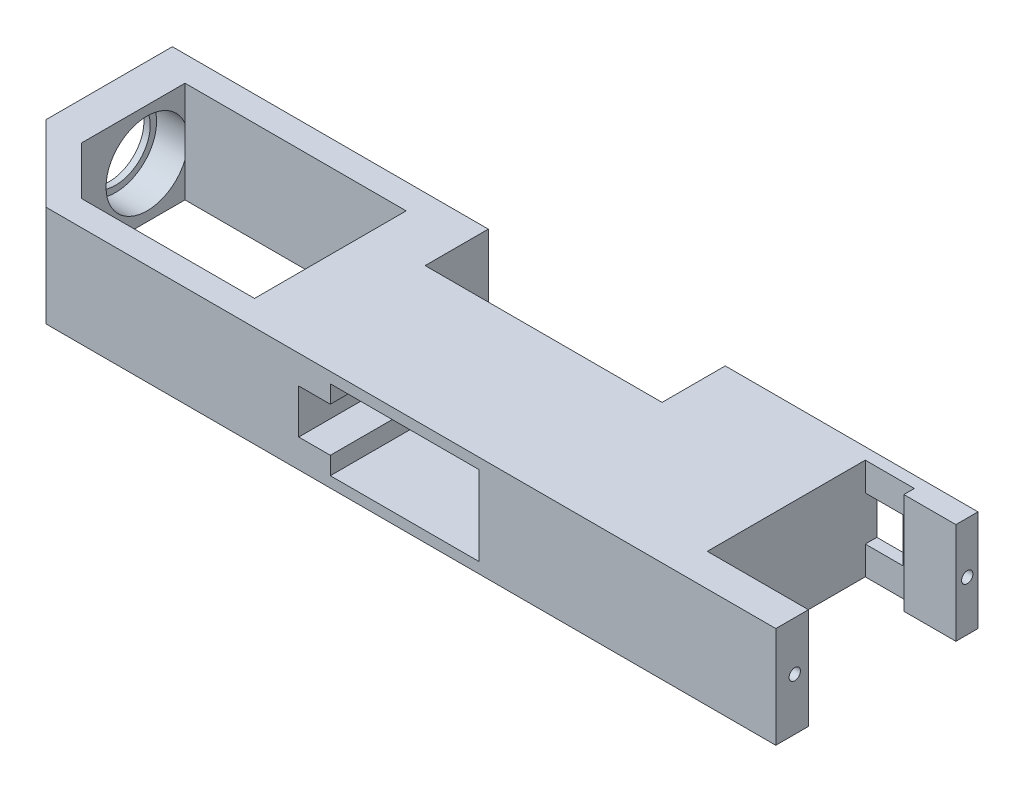
SolidWorks part; units mm, degrees
ref_plane "Front Plane" through (0, 0, 0) normal (0, 0, 1) x (1, 0, 0)
ref_plane "Top Plane" through (0, 0, 0) normal (0, 1, 0) x (1, 0, 0)
ref_plane "Right Plane" through (0, 0, 0) normal (1, 0, 0) x (0, 0, -1)
ref_axis "Axis1" through (0, 0, -88.99) along (0, 0, 1)
ref_axis "Axis2" through (88.99, 0, 0) along (-1, 0, 0)
sketch "Sketch1" plane through (0, 0, 0) normal (0, 1, 0) x (1, 0, 0)
  line L0 (64, -16.836) -> (47.9935, -16.836)
  line L1 (-63.5, 10) -> (64, 10)
  line L2 (-63.5, 10) -> (-63.5, -10)
  line L3 (-51.5, -22) -> (64, -22)
  line L4 (64, 10) -> (64, 6.5)
  line L5 (47.9935, -16.836) -> (47.9935, 8.164)
  line L6 (-63.5, -10) -> (-51.5, -22)
  line L8 (47.9935, 8.164) -> (55.7639, 8.164)
  line L9 (55.7639, 8.164) -> (55.7639, 6.5)
  line L10 (55.7639, 6.5) -> (64, 6.5)
  line L11 (64, -16.836) -> (64, -22)
  point P2 (-63.5, 0)
  dimension "D1" = 127.5
  dimension "D2" = 32
  dimension "D3" = 20
  dimension "D4" = 63.5
  dimension "D5" = 45
  dimension "D6" = 5.164
  dimension "D7" = 16.0065
  dimension "D8" = 25
  dimension "D9" = 3.5
  dimension "D10" = 8.2361
extrude "Boss-Extrude1" add sketch "Sketch1" along normal blind 8 and the other way blind 8
sketch "Sketch2" plane through (-63.5, 0, 0) normal (-1, 0, 0) x (0, 0, 1)
  circle A0 centre (0, 0) radius 5.5
  dimension "D1" = 11
extrude "Cut-Extrude1" cut sketch "Sketch2" against normal blind 8
sketch "Sketch3" plane through (0, 8, 0) normal (0, 1, 0) x (1, 0, 0)
  line L7 (-57.5, 6) -> (-22.5, 6)
  line L8 (-22.5, 6) -> (-22.5, -18)
  line L9 (-22.5, -18) -> (-49.8431, -18)
  line L10 (-49.8431, -18) -> (-57.5, -10.3431)
  line L11 (-57.5, -10.3431) -> (-57.5, 6)
  line L12 (-63.5, 10) -> (-63.5, -10) construction
  line L13 (-63.5, -10) -> (-51.5, -22) construction
  line L14 (64, 10) -> (-63.5, 10) construction
  line L15 (-51.5, -22) -> (64, -22) construction
  dimension "D1" = 6
  dimension "D2" = 4
  dimension "D3" = 4
  dimension "D4" = 4
  dimension "D5" = 35
extrude "Cut-Extrude2" cut sketch "Sketch3" against normal blind 16
sketch "Sketch4" plane through (-57.5, 0, 0) normal (1, 0, 0) x (0, 0, -1)
  circle A0 centre (0, 0) radius 6.5
  dimension "D1" = 13
extrude "Cut-Extrude3" cut sketch "Sketch4" against normal offset from surface (5 mm away) 1 contours A0 up to face at (-63.5, 0, 5.5)
sketch "Sketch5" plane through (0, 0, -10) normal (0, 0, -1) x (-1, 0, 0)
  line L0 (-64, 8) -> (63.5, 8) construction
  line L1 (-17, 6.3) -> (6.5, 6.3)
  line L2 (-17, 6.3) -> (-17, -6.3)
  line L3 (-17, -6.3) -> (6.5, -6.3)
  line L4 (6.5, 6.3) -> (6.5, -6.3)
  line L5 (-64, -8) -> (63.5, -8) construction
  line L6 (63.5, -8) -> (63.5, 8) construction
  dimension "D1" = 1.7
  dimension "D2" = 1.7
  dimension "D3" = 57
  dimension "D4" = 23.5
extrude "Cut-Extrude4" cut sketch "Sketch5" against normal through all
sketch "Sketch6" plane through (0, 0, -10) normal (0, 0, -1) x (-1, 0, 0)
  circle A0 centre (8.3, 0) radius 0.9
  circle A1 centre (-19, 0) radius 0.9
  dimension "D1" = 1.8
  dimension "D2" = 1.8
extrude "Cut-Extrude5" cut sketch "Sketch6" against normal blind 17
sketch "Sketch7" plane through (0, 0, -10) normal (0, 0, -1) x (-1, 0, 0)
  line L0 (-64, -8) -> (63.5, -8) construction
  line L1 (-47.9935, 3.5) -> (-53.9935, 3.5)
  line L2 (-47.9935, 3.5) -> (-47.9935, -3.5)
  line L3 (-47.9935, -3.5) -> (-53.9935, -3.5)
  line L4 (-53.9935, 3.5) -> (-53.9935, -3.5)
  point P4 (-47.9935, 0)
  dimension "D1" = 7
  dimension "D2" = 6
  dimension "D3" = 8
  dimension "D4" = 0
extrude "Cut-Extrude6" cut sketch "Sketch7" against normal blind 7
sketch "Sketch8" plane through (0, 0, 22) normal (0, 0, 1) x (1, 0, 0)
  line L0 (-6.5, -6.3) -> (-6.5, 6.3) construction
  line L1 (-6.5, -3.5) -> (-11.5, -3.5)
  line L2 (-6.5, -3.5) -> (-6.5, 3.5)
  line L3 (-6.5, 3.5) -> (-11.5, 3.5)
  line L4 (-11.5, -3.5) -> (-11.5, 3.5)
  point P7 (-6.5, 0)
  point P8 (-6.5, 0)
  dimension "D1" = 5
  dimension "D2" = 7
extrude "Cut-Extrude7" cut sketch "Sketch8" against normal blind 10
sketch "Sketch9" plane through (64, 0, 0) normal (1, 0, 0) x (0, 0, -1)
  circle A0 centre (-18.9984, 0.247) radius 0.9
  circle A1 centre (8.2993, -0.1079) radius 0.9
  dimension "D1" = 1.8
  dimension "D2" = 1.8
extrude "Cut-Extrude8" cut sketch "Sketch9" against normal blind 7
sketch "Sketch10" plane through (0, 0, -10) normal (0, 0, -1) x (-1, 0, 0)
  line L0 (13.5, -8) -> (13.5, 8)
  line L1 (-64, -8) -> (63.5, -8) construction
  line L2 (-64, 8) -> (63.5, 8) construction
  line L3 (13.5, 8) -> (-24, 8)
  line L4 (-24, 8) -> (-24, -8)
  line L5 (-24, -8) -> (13.5, -8)
  line L6 (63.5, -8) -> (63.5, 8) construction
  line L7 (-64, -8) -> (-64, 8) construction
  dimension "D1" = 50
  dimension "D2" = 40
extrude "Cut-Extrude9" cut sketch "Sketch10" against normal blind 10
